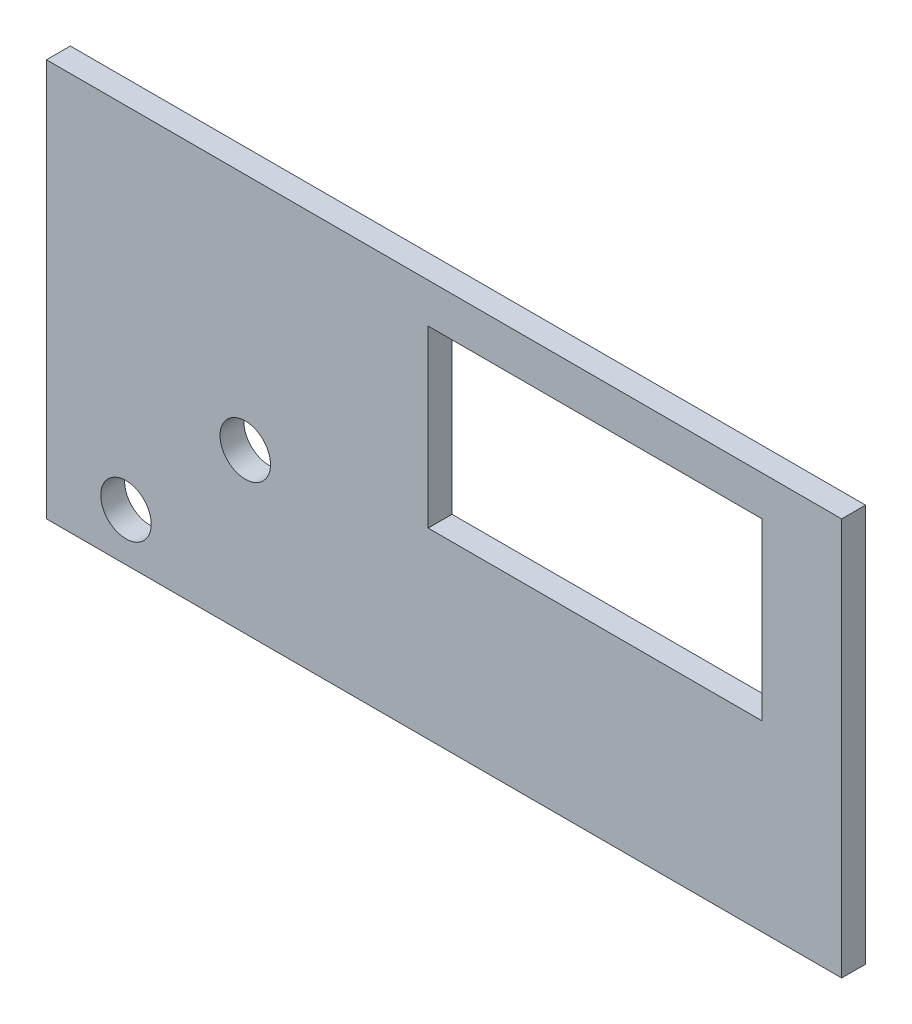
SolidWorks part; units mm, degrees
ref_plane "Front Plane" through (0, 0, 0) normal (0, 0, 1) x (1, 0, 0)
ref_plane "Top Plane" through (0, 0, 0) normal (0, 1, 0) x (1, 0, 0)
ref_plane "Right Plane" through (0, 0, 0) normal (1, 0, 0) x (0, 0, -1)
sketch "Sketch1" plane through (0, 0, 0) normal (0, 0, 1) x (1, 0, 0)
  line L1 (0, 0) -> (100, 0)
  line L2 (0, 0) -> (0, -50)
  line L3 (0, -50) -> (100, -50)
  line L4 (100, 0) -> (100, -50)
  dimension "D1" = 100
  dimension "D2" = 50
extrude "Boss-Extrude1" add sketch "Sketch1" along normal blind 3
sketch "Sketch2" plane through (0, 0, 3) normal (0, 0, 1) x (1, 0, 0)
  line L0 (0, -50) -> (100, -50) construction
  line L3 (0, -50) -> (100, -50) construction
  line L4 (0, 0) -> (0, -50) construction
  line L5 (100, 0) -> (0, 0) construction
  line L6 (48, -5) -> (90, -5)
  line L7 (48, -5) -> (48, -27)
  line L8 (48, -27) -> (90, -27)
  line L9 (90, -5) -> (90, -27)
  line L10 (100, -50) -> (100, 0) construction
  circle A0 centre (25, -30) radius 3.175
  circle A1 centre (10, -44) radius 3.175
  dimension "D1" = 6.35
  dimension "D4" = 6.35
  dimension "D2" = 20
  dimension "D3" = 25
  dimension "D5" = 6
  dimension "D6" = 10
  dimension "D7" = 42
  dimension "D8" = 22
  dimension "D9" = 5
  dimension "D10" = 10
extrude "Cut-Extrude1" cut sketch "Sketch2" against normal through all
